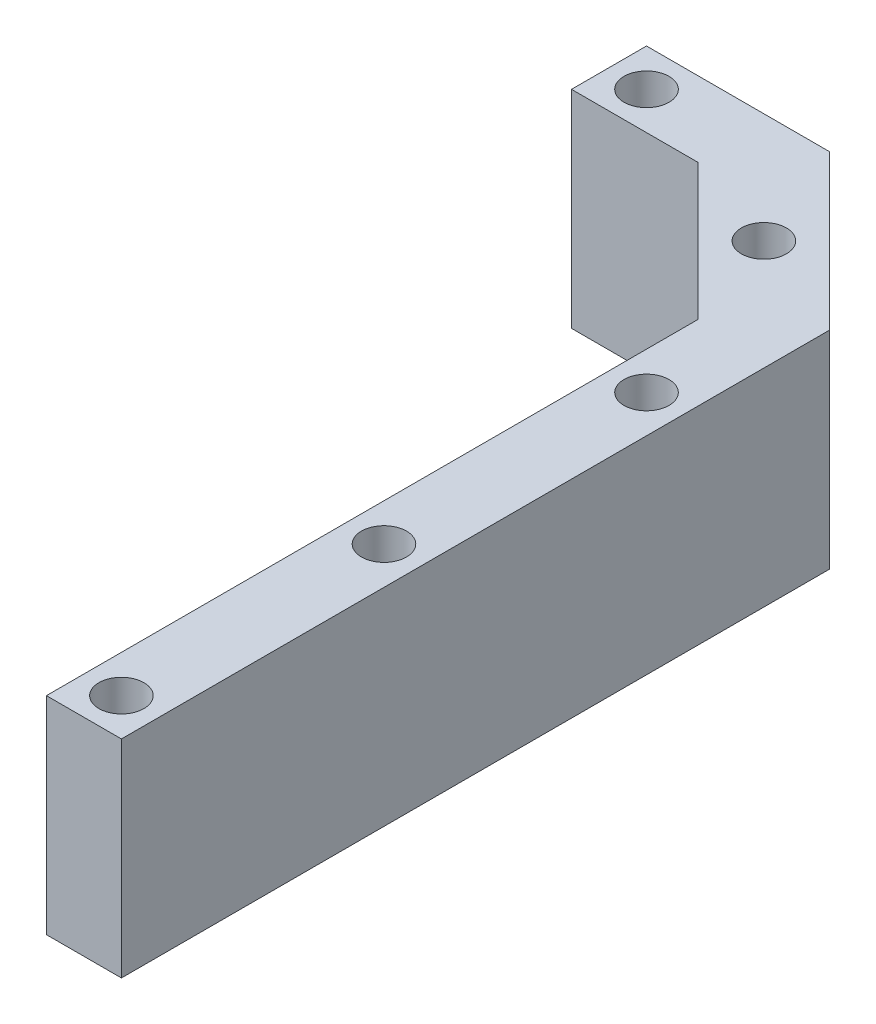
SolidWorks part; units mm, degrees
ref_plane "前视基准面" through (0, 0, 0) normal (0, 0, 1) x (1, 0, 0)
ref_plane "上视基准面" through (0, 0, 0) normal (0, 1, 0) x (1, 0, 0)
ref_plane "右视基准面" through (0, 0, 0) normal (1, 0, 0) x (0, 0, -1)
other "Configuration Table"
sketch "草图2" plane through (0, 0, 0) normal (0, 1, 0) x (1, 0, 0)
  line L0 (0, -20.8431) -> (0, -49.1569) construction
  line L1 (-35, 35) -> (35, 35) construction
  line L2 (-35, 35) -> (-35, -35) construction
  line L3 (-35, -35) -> (35, -35) construction
  line L4 (35, 35) -> (35, -35) construction
  line L5 (-35, 35) -> (35, -35) construction
  line L6 (-35, -35) -> (35, 35) construction
  line L7 (-49.9747, 0) -> (-20.0253, 0) construction
  line L9 (-37.5, -15) -> (-37.5, -20)
  line L13 (-15, -37.5) -> (-15, -25.2969)
  line L14 (-15, -25.2969) -> (-25.2969, -15)
  line L17 (-37.5, -20) -> (-29.054, -20)
  line L18 (-29.054, -20) -> (-20, -29.054)
  line L19 (-20, -29.054) -> (-20, -37.5)
  line L25 (-37.5, -15) -> (-25.2969, -15)
  line L26 (-20, -37.5) -> (-20, -72.5)
  line L27 (-20, -72.5) -> (-15, -72.5)
  line L28 (-15, -72.5) -> (-15, -37.5)
  circle A0 centre (-35, -17.5) radius 1.5
  circle A1 centre (-17.5, -35) radius 1.5
  circle A3 centre (-17.5, -52.5) radius 1.5
  circle A4 centre (-17.5, -70) radius 1.5
  point P0 (0, 0)
  point P9 (0, -35)
  point P12 (-35, 0)
  dimension "D3" = 3
  dimension "D4" = 17.5
  dimension "D5" = 17.5
  dimension "D6" = 3
  dimension "D1" = 70
  dimension "D2" = 70
  dimension "D7" = 2.5
  dimension "D8" = 17.5
  dimension "D9" = 2
  dimension "D10" = 2.5
  dimension "D11" = 2.5
extrude "凸台-拉伸1" add sketch "草图2" along normal blind 13.8
sketch "草图3" plane through (0, 13.8, 0) normal (0, 1, 0) x (1, 0, 0)
  line L0 (-25.2969, -15) -> (-29.054, -20) construction
  line L1 (-15, -25.2969) -> (-20, -29.054) construction
  line L2 (-27.1754, -17.5) -> (-17.5, -27.1754) construction
  line L3 (-22.3377, -22.3377) -> (-24.527, -24.527) construction
  line L4 (-29.054, -20) -> (-20, -29.054) construction
  circle A0 centre (-22.3377, -22.3377) radius 1.5
  dimension "D1" = 3
extrude "切除-拉伸1" cut sketch "草图3" against normal up to next contours A0
sketch "草图4" plane through (-20.1485, 0, 20.1485) normal (0.7071, 0, -0.7071) x (-0.7071, 0, -0.7071)
  line L0 (0, 0) -> (0, 31.7252) construction
  line L1 (-4.8965, 10.5539) -> (4.8965, 10.5539)
  line L2 (-4.8965, 10.5539) -> (-4.8965, 3.2461)
  line L3 (-4.8965, 3.2461) -> (4.8965, 3.2461)
  line L4 (4.8965, 10.5539) -> (4.8965, 3.2461)
  line L5 (-7.281, 6.9) -> (31.4921, 6.9) construction
  line L6 (-7.281, 13.8) -> (-7.281, 0) construction
extrude "切除-拉伸2" cut sketch "草图4" against normal through all
